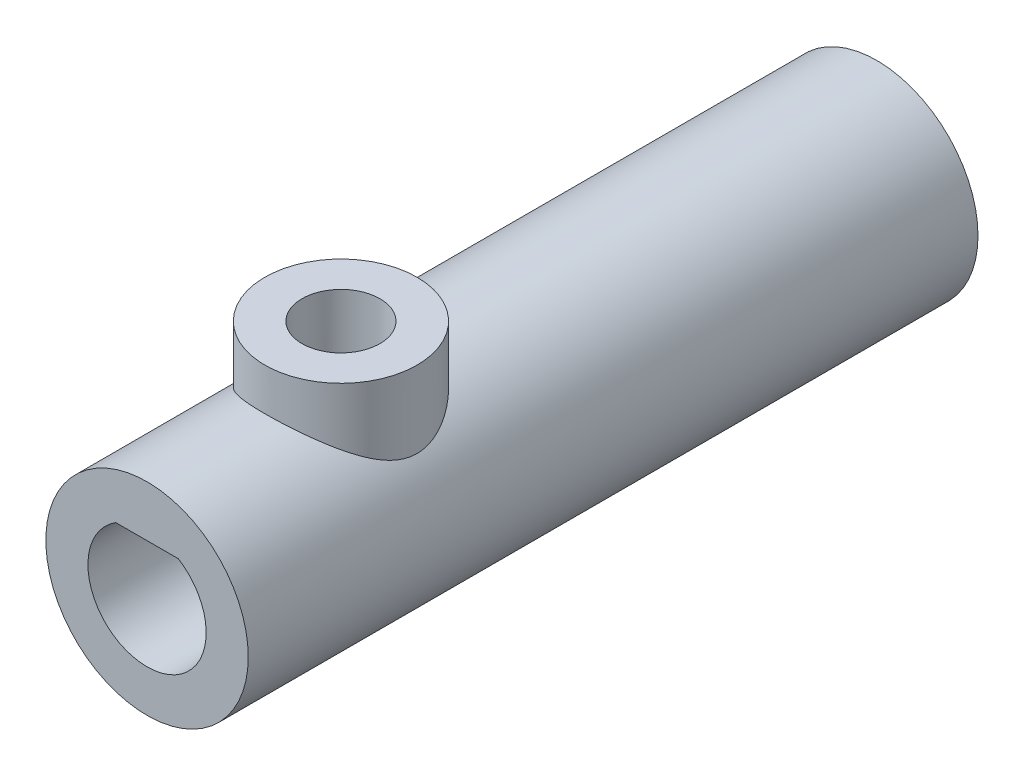
SolidWorks part; units mm, degrees
note: The reader was unsure of these and kept them because the rebuilt part matched: shared geometry of "Sketch5<2>".
ref_plane "Front Plane" through (0, 0, 0) normal (0, 0, 1) x (1, 0, 0)
ref_plane "Top Plane" through (0, 0, 0) normal (0, 1, 0) x (1, 0, 0)
ref_plane "Right Plane" through (0, 0, 0) normal (1, 0, 0) x (0, 0, -1)
sketch "Sketch1" plane through (0, 0, 0) normal (0, 0, 1) x (1, 0, 0)
  circle A0 centre (0, 0) radius 3.65 construction
  circle A1 centre (0, 0) radius 5.65
  circle A2 centre (0, 0) radius 1.55
  circle A3 centre (0, 0) radius 3.65 construction
  arc A4 (-1.2776, -2.7957) -> (-1.2728, -2.7489) centre (-1.7505, -2.7239) ccw
  arc A5 (-0.4154, -3.0006) -> (-0.4367, -3.0426) centre (0, -3.2379) ccw
  arc A6 (0.4154, -3.0006) -> (-0.4154, -3.0006) centre (0, -3.2379) ccw
  arc A7 (0.4367, -3.0426) -> (0.4154, -3.0006) centre (0, -3.2379) ccw
  arc A8 (1.2728, -2.7489) -> (1.2776, -2.7957) centre (1.7505, -2.7239) ccw
  arc A9 (2.0123, -2.3235) -> (1.9717, -2.2997) centre (1.7505, -2.7239) ccw
  arc A10 (2.9491, -0.8667) -> (2.902, -0.8686) centre (2.9453, -1.3451) ccw
  arc A11 (2.5569, -1.6244) -> (2.5862, -1.6612) centre (2.9453, -1.3451) ccw
  arc A12 (3.0292, 0.0158) -> (3.0738, 0.0007) centre (3.2049, 0.4608) ccw
  arc A13 (2.9495, 0.8653) -> (2.911, 0.8382) centre (3.2049, 0.4608) ccw
  arc A14 (2.9491, -0.8667) -> (3.5766, -0.7323) centre (2.9608, 0.6111) ccw
  arc A15 (2.902, -0.8686) -> (2.5569, -1.6244) centre (2.9453, -1.3451) ccw
  arc A16 (2.8956, -2.2234) -> (2.5862, -1.6612) centre (1.4771, -2.6378) ccw
  arc A17 (2.6129, -2.5497) -> (2.8956, -2.2234) centre (0, 0) ccw
  arc A18 (2.0123, -2.3235) -> (2.6129, -2.5497) centre (2.8211, -1.0866) ccw
  arc A19 (1.9717, -2.2997) -> (1.2728, -2.7489) centre (1.7505, -2.7239) ccw
  arc A20 (1.2339, -3.436) -> (1.2776, -2.7957) centre (-0.1835, -3.0176) ccw
  arc A21 (0.8196, -3.5576) -> (1.2339, -3.436) centre (0, 0) ccw
  arc A22 (0.4367, -3.0426) -> (0.8196, -3.5576) centre (1.7858, -2.4394) ccw
  arc A23 (-0.8196, -3.5576) -> (-0.4367, -3.0426) centre (-1.7858, -2.4394) ccw
  arc A24 (-1.2339, -3.436) -> (-0.8196, -3.5576) centre (0, 0) ccw
  arc A25 (-1.2776, -2.7957) -> (-1.2339, -3.436) centre (0.1835, -3.0176) ccw
  arc A26 (3.5766, -0.7323) -> (3.638, -0.305) centre (0, 0) ccw
  arc A27 (3.638, -0.305) -> (3.0738, 0.0007) centre (2.6687, -1.4205) ccw
  arc A28 (2.911, 0.8382) -> (3.0292, 0.0158) centre (3.2049, 0.4608) ccw
  arc A29 (2.9495, 0.8653) -> (3.4047, 1.3176) centre (2.1604, 2.1148) ccw
  arc A30 (3.4047, 1.3176) -> (3.2254, 1.7103) centre (0, 0) ccw
  arc A31 (-1.9717, -2.2997) -> (-2.0123, -2.3235) centre (-1.7505, -2.7239) ccw
  arc A32 (-2.5862, -1.6612) -> (-2.5569, -1.6244) centre (-2.9453, -1.3451) ccw
  arc A33 (-2.902, -0.8686) -> (-2.9491, -0.8667) centre (-2.9453, -1.3451) ccw
  arc A34 (-3.0738, 0.0007) -> (-3.0292, 0.0158) centre (-3.2049, 0.4608) ccw
  arc A35 (-2.911, 0.8382) -> (-2.9495, 0.8653) centre (-3.2049, 0.4608) ccw
  arc A36 (-1.2728, -2.7489) -> (-1.9717, -2.2997) centre (-1.7505, -2.7239) ccw
  arc A37 (-2.6129, -2.5497) -> (-2.0123, -2.3235) centre (-2.8211, -1.0866) ccw
  arc A38 (-2.8956, -2.2234) -> (-2.6129, -2.5497) centre (0, 0) ccw
  arc A39 (-2.5862, -1.6612) -> (-2.8956, -2.2234) centre (-1.4771, -2.6378) ccw
  arc A40 (-2.5569, -1.6244) -> (-2.902, -0.8686) centre (-2.9453, -1.3451) ccw
  arc A41 (-3.5766, -0.7323) -> (-2.9491, -0.8667) centre (-2.9608, 0.6111) ccw
  arc A42 (-3.638, -0.305) -> (-3.5766, -0.7323) centre (0, 0) ccw
  arc A43 (-3.0738, 0.0007) -> (-3.638, -0.305) centre (-2.6687, -1.4205) ccw
  arc A44 (-3.0292, 0.0158) -> (-2.911, 0.8382) centre (-3.2049, 0.4608) ccw
  arc A45 (-3.4047, 1.3176) -> (-2.9495, 0.8653) centre (-2.1604, 2.1148) ccw
  arc A46 (-2.5854, 1.6624) -> (-2.5398, 1.651) centre (-2.447, 2.1203) ccw
  arc A47 (-1.9957, 2.279) -> (-2.0134, 2.3225) centre (-2.447, 2.1203) ccw
  arc A48 (-1.2762, 2.7963) -> (-1.244, 2.762) centre (-0.9122, 3.1067) ccw
  arc A49 (-0.4468, 2.9961) -> (-0.4382, 3.0424) centre (-0.9122, 3.1067) ccw
  arc A50 (2.5398, 1.651) -> (2.5854, 1.6624) centre (2.447, 2.1203) ccw
  arc A51 (2.0134, 2.3225) -> (1.9957, 2.279) centre (2.447, 2.1203) ccw
  arc A52 (3.2254, 1.7103) -> (2.5854, 1.6624) centre (3.013, 0.2478) ccw
  arc A53 (1.9957, 2.279) -> (2.5398, 1.651) centre (2.447, 2.1203) ccw
  arc A54 (2.0134, 2.3225) -> (2.1519, 2.9492) centre (0.6741, 2.9471) ccw
  arc A55 (2.1519, 2.9492) -> (1.7887, 3.1826) centre (0, 0) ccw
  arc A56 (1.244, 2.762) -> (1.2762, 2.7963) centre (0.9122, 3.1067) ccw
  arc A57 (0.4382, 3.0424) -> (0.4468, 2.9961) centre (0.9122, 3.1067) ccw
  arc A58 (1.7887, 3.1826) -> (1.2762, 2.7963) centre (2.4007, 1.8374) ccw
  arc A59 (0.4468, 2.9961) -> (1.244, 2.762) centre (0.9122, 3.1067) ccw
  arc A60 (0.4382, 3.0424) -> (0.2158, 3.6444) centre (-1.0262, 2.8437) ccw
  arc A61 (0.2158, 3.6444) -> (0, 3.6508) centre (0, 0) ccw
  arc A62 (0, 3.6508) -> (-0.2158, 3.6444) centre (0, 0) ccw
  arc A63 (-0.2158, 3.6444) -> (-0.4382, 3.0424) centre (1.0262, 2.8437) ccw
  arc A64 (-1.244, 2.762) -> (-0.4468, 2.9961) centre (-0.9122, 3.1067) ccw
  arc A65 (-1.2762, 2.7963) -> (-1.7887, 3.1826) centre (-2.4007, 1.8374) ccw
  arc A66 (-1.7887, 3.1826) -> (-2.1519, 2.9492) centre (0, 0) ccw
  arc A67 (-2.1519, 2.9492) -> (-2.0134, 2.3225) centre (-0.6741, 2.9471) ccw
  arc A68 (-2.5398, 1.651) -> (-1.9957, 2.279) centre (-2.447, 2.1203) ccw
  arc A69 (-2.5854, 1.6624) -> (-3.2254, 1.7103) centre (-3.013, 0.2478) ccw
  arc A70 (-3.2254, 1.7103) -> (-3.4047, 1.3176) centre (0, 0) ccw
  circle A71 centre (0, 0) radius 3.6508
  point P4 (0, 3.65)
  point P9 (0, 5.65)
  dimension "D3" = 7.3
extrude "Boss-Extrude1" add sketch "Sketch1" along normal blind 12 contours A1 A71 A30 A26 A17 A21 A24 A38 A42 A70 A66 A62 A61 A55 | A67 A71 A69 A46 A68 A47 | A63 A71 A65 A48 A64 A49 | A58 A71 A60 A57 A59 A56 | A52 A71 A54 A51 A53 A50 | A27 A71 A29 A13 A28 A12 | A16 A71 A14 A10 A15 A11 | A20 A71 A18 A9 A19 A8 | A23 A71 A22 A7 A6 A5 | A37 A71 A25 A4 A36 A31 | A41 A71 A39 A32 A40 A33 | A45 A71 A43 A34 A44 A35
sketch "Sketch2" plane through (0, 0, 12) normal (0, 0, 1) x (1, 0, 0)
  circle A0 centre (0, 0) radius 5.65
extrude "Boss-Extrude2" add sketch "Sketch2" along normal blind 14.74
sketch "Sketch3" plane through (0, 0, 26.74) normal (0, 0, 1) x (1, 0, 0)
  line L0 (-1.6583, 2.5) -> (1.6583, 2.5) construction
  line L1 (-1.7464, 2.8) -> (1.7464, 2.8)
  circle A0 centre (0, 0) radius 3 construction
  circle A1 centre (0, 0) radius 5.65
  arc A2 (-1.6583, 2.5) -> (1.6583, 2.5) centre (0, 0) ccw construction
  arc A3 (-1.7464, 2.8) -> (1.7464, 2.8) centre (0, 0) ccw
  circle A4 centre (0, 0) radius 3.3 construction
  point P5 (0, 2.5)
  dimension "D1" = 6
  dimension "D2" = 2.5
  dimension "D4" = 0.3
  dimension "D3" = 0.3
extrude "Boss-Extrude3" add sketch "Sketch3" along normal blind 14 contours L0 A2
sketch "Sketch5" plane through (0, 2.8, 0) normal (0, -1, 0) x (1, 0, 0)
  line L0 (0, 26.74) -> (0, 40.74) construction
  line L4 (-1.7464, 26.74) -> (1.7464, 26.74)
  line L5 (1.7464, 26.74) -> (1.7464, 40.74)
  line L6 (1.7464, 40.74) -> (-1.7464, 40.74)
  line L7 (-1.7464, 40.74) -> (-1.7464, 26.74)
  line L8 (-1.7464, 26.74) -> (1.7464, 26.74) construction
  line L9 (1.7464, 26.74) -> (1.7464, 40.74) construction
  line L10 (1.7464, 40.74) -> (-1.7464, 40.74) construction
  line L11 (-1.7464, 40.74) -> (-1.7464, 26.74) construction
  circle A0 centre (0, 29.915) radius 2.175
  circle A1 centre (0, 29.915) radius 4.25
  dimension "D2" = 1
  dimension "D3" = 4.35
  dimension "D4" = 8.5
  dimension "D1" = 0
extrude "Boss-Extrude4" add sketch "Sketch5" against normal blind 5.2
extrude "Cut-Extrude1" cut sketch "Sketch5<2>" against normal through all contours A0
sketch "Sketch5<2>" plane through (0, 2.8, 0) normal (0, -1, 0) x (1, 0, 0) same geometry as "Sketch5"
